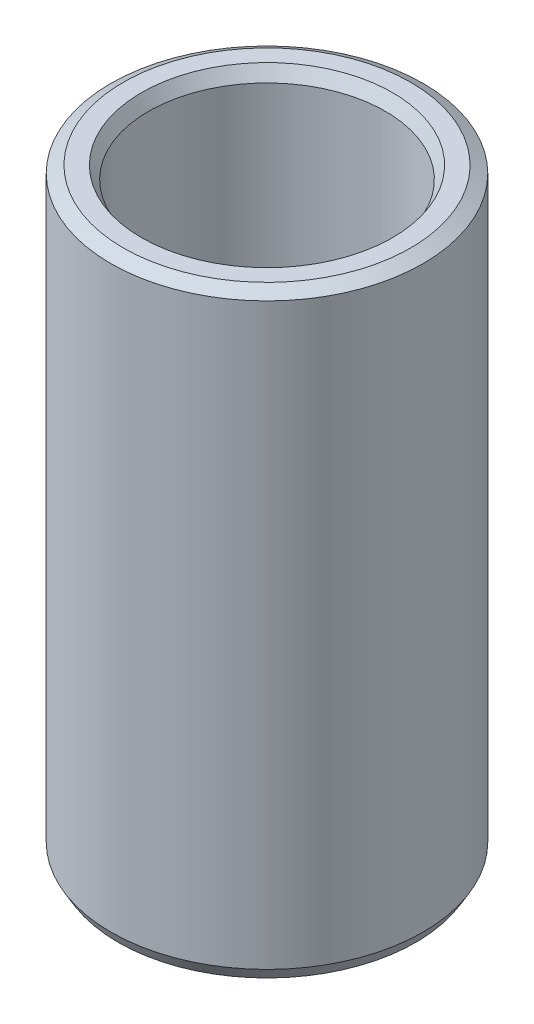
SolidWorks part; units mm, degrees
ref_plane "Front Plane" through (0, 0, 0) normal (0, 0, 1) x (1, 0, 0)
ref_plane "Top Plane" through (0, 0, 0) normal (0, 1, 0) x (1, 0, 0)
ref_plane "Right Plane" through (0, 0, 0) normal (1, 0, 0) x (0, 0, -1)
sketch "Sketch1" plane through (0, 0, 0) normal (0, 1, 0) x (1, 0, 0)
  circle A0 centre (0, 0) radius 12.5
  dimension "SLEEVE_OD" = 25
extrude "Boss-Extrude1" add sketch "Sketch1" along normal blind 47.9326
sketch "Sketch2" plane through (0, 0, 0) normal (0, 1, 0) x (1, 0, 0)
  circle A0 centre (0, 0) radius 9.4777
  dimension "BORE_D" = 18.9553
extrude "Cut-Extrude1" cut sketch "Sketch2" along normal through all
chamfer "Chamfer1" distance 0.5791 angle 60 4 edges at (0, 47.9326, 9.4777) (0, 0, 9.4777) (0, 0, 12.5) (0, 47.9326, 12.5) first distance on face at (0, 47.9326, 9.4777) first distance on face at (0, 0, 9.4777) first distance on face at (0, 47.9326, 12.5)
